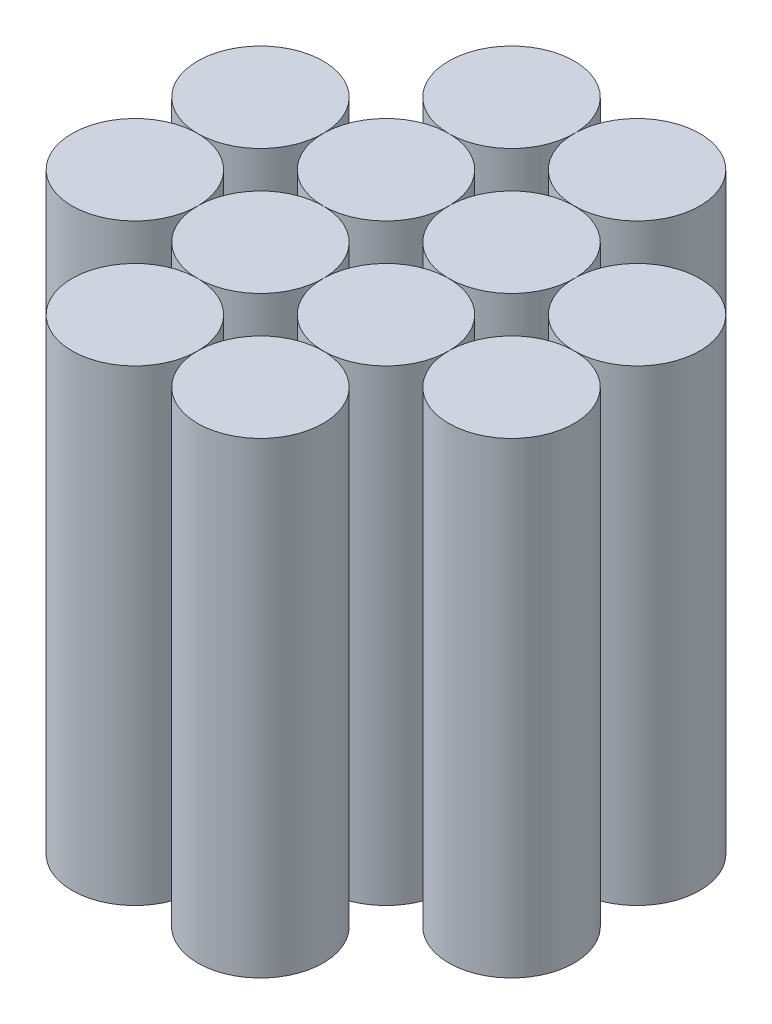
SolidWorks part; units mm, degrees
ref_plane "Front Plane" through (0, 0, 0) normal (0, 0, 1) x (1, 0, 0)
ref_plane "Top Plane" through (0, 0, 0) normal (0, 1, 0) x (1, 0, 0)
ref_plane "Right Plane" through (0, 0, 0) normal (1, 0, 0) x (0, 0, -1)
sketch "Sketch1" plane through (0, 0, 0) normal (0, 1, 0) x (1, 0, 0)
  line L0 (-18, 0) -> (0, 0) construction
  line L17 (0, 0) -> (0, 18) construction
  line L18 (0, 18) -> (18, 18) construction
  line L19 (18, 18) -> (18, 0) construction
  line L20 (18, 0) -> (36, 0) construction
  line L21 (36, 0) -> (36, -18) construction
  line L22 (36, -18) -> (18, -18) construction
  line L23 (18, -18) -> (18, -36) construction
  line L24 (18, -36) -> (0, -36) construction
  line L25 (0, -36) -> (0, -18) construction
  line L26 (0, -18) -> (-18, -18) construction
  line L27 (-18, -18) -> (-18, 0) construction
  circle A14 centre (-18, 0) radius 9
  circle A15 centre (18, 18) radius 9
  circle A16 centre (0, 18) radius 9
  circle A17 centre (0, 0) radius 9
  circle A18 centre (18, 0) radius 9
  circle A19 centre (36, 0) radius 9
  circle A20 centre (18, -18) radius 9
  circle A21 centre (36, -18) radius 9
  circle A22 centre (-18, -18) radius 9
  circle A23 centre (0, -18) radius 9
  circle A24 centre (0, -36) radius 9
  circle A25 centre (18, -36) radius 9
  point P3 (0, -18)
  point P4 (0, 0)
  point P5 (0, -36)
  point P6 (18, 0)
  point P7 (18, -36)
  point P8 (18, 18)
  point P9 (18, -18)
  point P10 (36, -18)
  point P11 (36, 0)
  point P12 (0, 18)
  point P13 (-18, 0)
  point P14 (-18, -18)
  dimension "D1" = 18
  dimension "D2" = 18
extrude "Boss-Extrude1" add sketch "Sketch1" along normal blind 67 contours A14 | A17 | A16 | A15 | A18 | A19 | A21 | A20 | A25 | A24 | A23 | A22 region at (-18, 0, 0)
